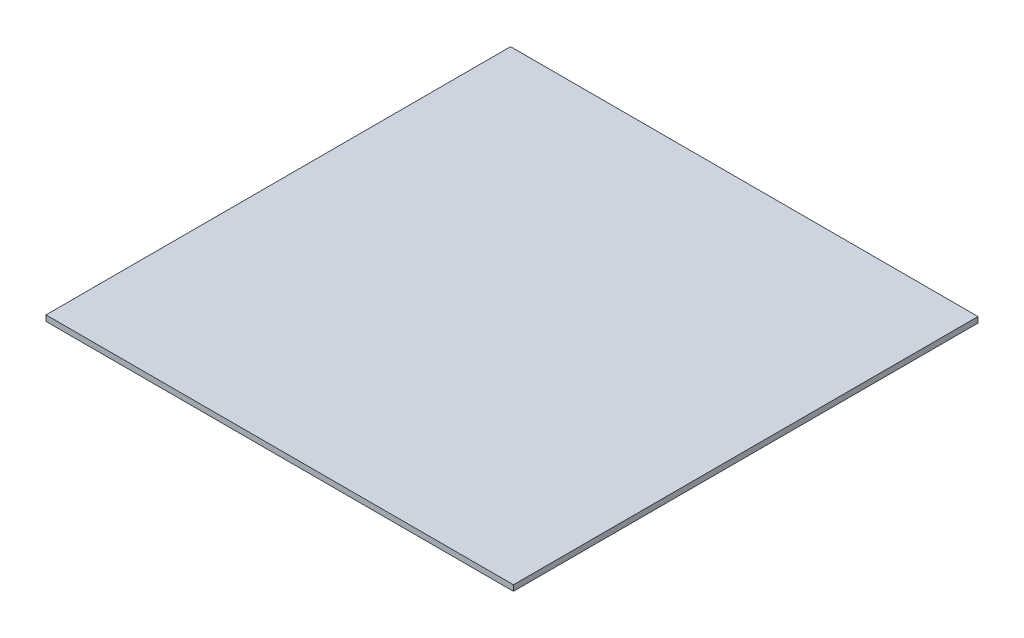
SolidWorks part; units mm, degrees
ref_plane "前视基准面" through (0, 0, 0) normal (0, 0, 1) x (1, 0, 0)
ref_plane "上视基准面" through (0, 0, 0) normal (0, 1, 0) x (1, 0, 0)
ref_plane "右视基准面" through (0, 0, 0) normal (1, 0, 0) x (0, 0, -1)
sketch "草图1" plane through (0, 0, 0) normal (0, 1, 0) x (1, 0, 0)
  line L1 (0, 0) -> (246, 0)
  line L2 (0, 0) -> (0, -244.5)
  line L3 (0, -244.5) -> (246, -244.5)
  line L4 (246, 0) -> (246, -244.5)
  dimension "D1" = 246
  dimension "D2" = 244.5
extrude "凸台-拉伸1" add sketch "草图1" along normal blind 3
